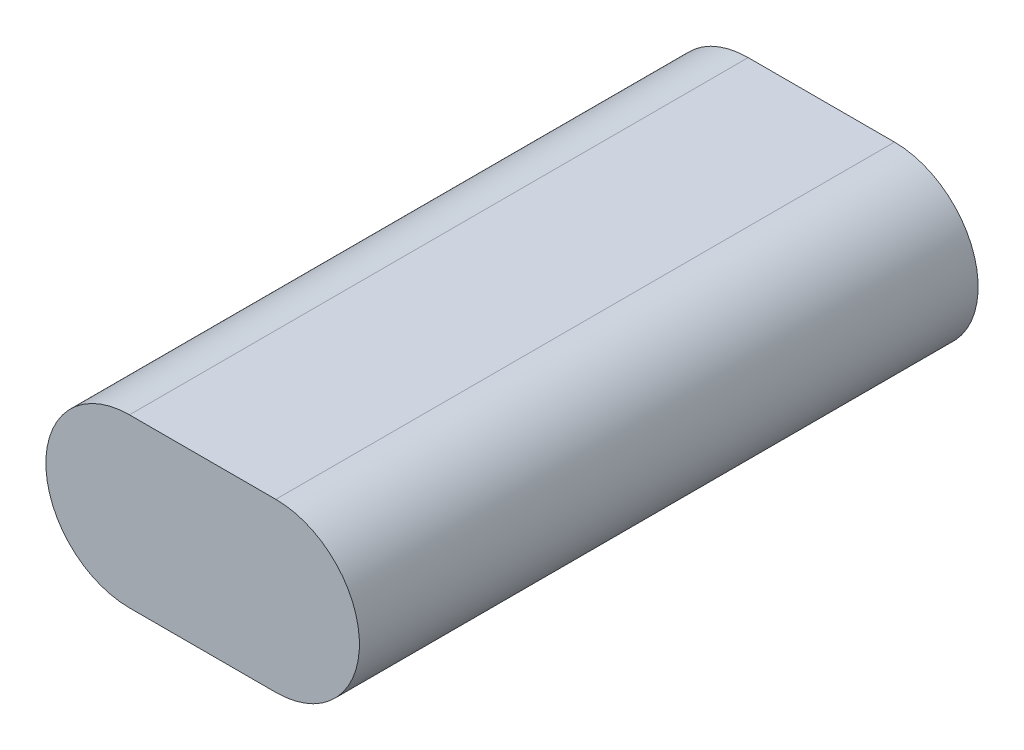
SolidWorks part; units mm, degrees
ref_plane "Front Plane" through (0, 0, 0) normal (0, 0, 1) x (1, 0, 0)
ref_plane "Top Plane" through (0, 0, 0) normal (0, 1, 0) x (1, 0, 0)
ref_plane "Right Plane" through (0, 0, 0) normal (1, 0, 0) x (0, 0, -1)
sketch "Sketch1" plane through (0, 0, 0) normal (0, 1, 0) x (1, 0, 0)
  line L1 (-18.75, 37) -> (18.75, 37)
  line L2 (-18.75, 37) -> (-18.75, -37)
  line L3 (-18.75, -37) -> (18.75, -37)
  line L4 (18.75, 37) -> (18.75, -37)
  point P4 (0, 37)
  point P6 (18.75, 0)
  dimension "D1" = 37.5
  dimension "D2" = 74
extrude "Boss-Extrude1" add sketch "Sketch1" along normal blind 20
fillet "Fillet3" 2 edges at (-18.75, 20, 0) (-18.75, 0, 0) type full round first side face at (0, 20, 0) second side face at (0, 0, 0) middle face at (-18.75, 10, 0)
fillet "Fillet4" 2 edges at (18.75, 20, 0) (18.75, 0, 0) type full round first side face at (5, 20, 0) second side face at (5, 0, 0) middle face at (18.75, 10, 0)
